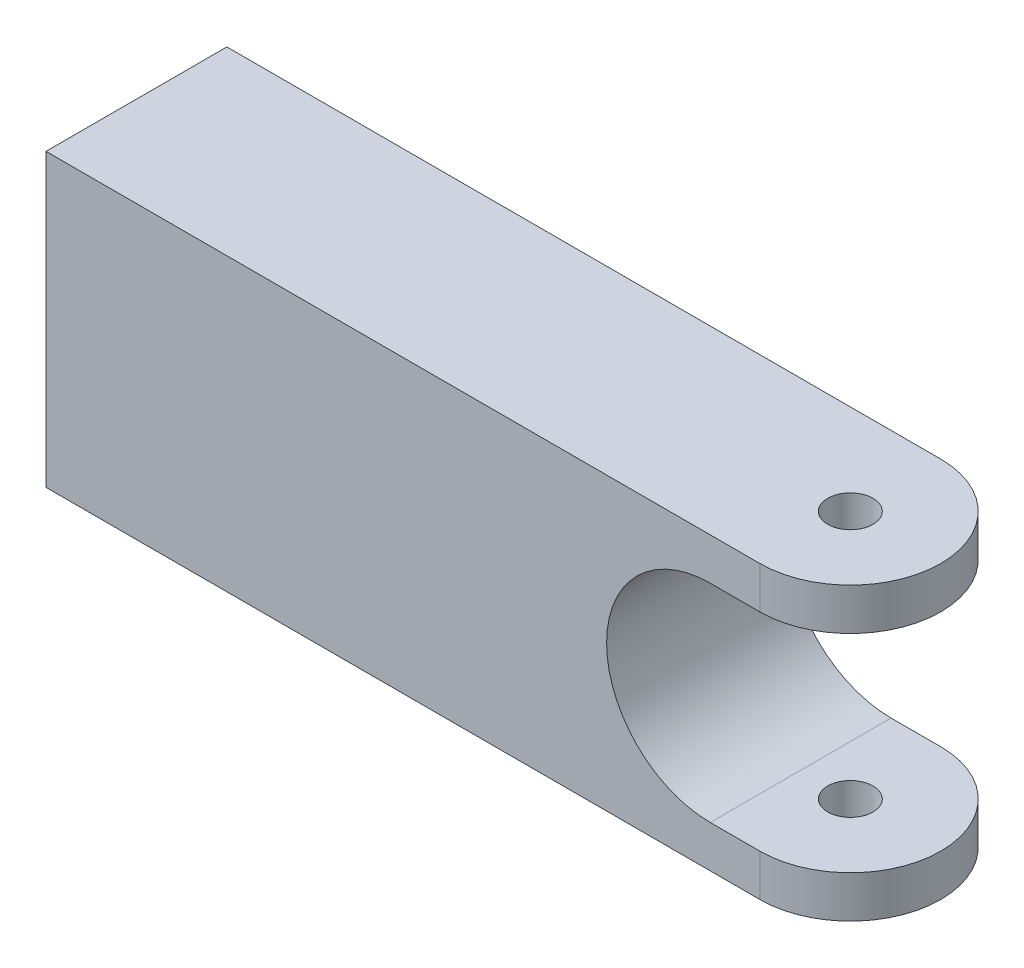
SolidWorks part; units mm, degrees
ref_plane "Front Plane" through (0, 0, 0) normal (0, 0, 1) x (1, 0, 0)
ref_plane "Top Plane" through (0, 0, 0) normal (0, 1, 0) x (1, 0, 0)
ref_plane "Right Plane" through (0, 0, 0) normal (1, 0, 0) x (0, 0, -1)
sketch "Sketch1" plane through (0, 0, 0) normal (0, 0, 1) x (1, 0, 0)
  line L0 (0, 0) -> (101.6, 0) construction
  line L1 (55, 0) -> (-55, 0) construction
  line L2 (0, 0) -> (0, -80.01) construction
  line L3 (0, -55) -> (0, 55) construction
  line L4 (74.0826, -4.3688) -> (74.0826, 0) construction
  line L5 (0, 0) -> (83.82, 0)
  line L6 (0, 0) -> (0, -30.3276)
  line L7 (0, -30.3276) -> (83.82, -30.3276)
  line L8 (83.82, 0) -> (83.82, -4.3688)
  line L9 (83.82, -4.3688) -> (69.215, -4.3688)
  line L11 (83.82, -25.9588) -> (69.215, -25.9588)
  line L13 (74.7837, -25.9588) -> (74.7837, -30.3276) construction
  line L14 (83.82, -25.9588) -> (83.82, -30.3276)
  arc A0 (0, -80.01) -> (101.6, 0) centre (-12.2194, 40.0196) ccw construction
  arc A1 (69.215, -4.3688) -> (69.215, -25.9588) centre (69.215, -15.1638) ccw
  point P13 (0, 0)
  dimension "D3" = 120.65
  dimension "D6" = 21.59
  dimension "D7" = 14.605
  dimension "D1" = 80.01
  dimension "D2" = 101.6
  dimension "D4" = 83.82
  dimension "D5" = 30.3276
extrude "Boss-Extrude1" add sketch "Sketch1" along normal blind 18.8468
sketch "Sketch3" plane through (0, 0, 0) normal (0, 1, 0) x (1, 0, 0)
  line L0 (-16.6802, 0) -> (16.6802, 0) construction
  line L1 (83.82, -18.8468) -> (0, -18.8468) construction
  line L2 (83.82, -18.8468) -> (83.82, 0) construction
  line L5 (85.1916, -18.8468) -> (74.3966, -18.8468)
  line L6 (74.3966, 0) -> (85.1916, 0)
  line L7 (85.1916, 0) -> (85.1916, -18.8468)
  arc A0 (74.3966, 0) -> (74.3966, -18.8468) centre (74.3966, -9.4234) cw
  circle A1 centre (74.3966, -9.4234) radius 2.3559
  dimension "D1" = 4.7117
  dimension "D2" = 10.795
extrude "Cut-Extrude1" cut sketch "Sketch3" against normal through all
